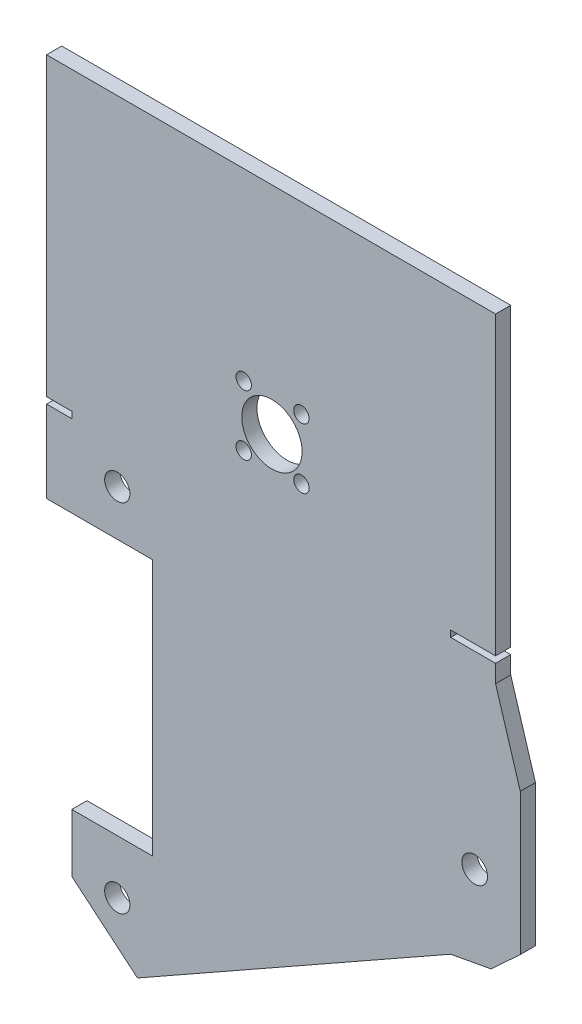
SolidWorks part; units mm, degrees
ref_plane "Front Plane" through (0, 0, 0) normal (0, 0, 1) x (1, 0, 0)
ref_plane "Top Plane" through (0, 0, 0) normal (0, 1, 0) x (1, 0, 0)
ref_plane "Right Plane" through (0, 0, 0) normal (1, 0, 0) x (0, 0, -1)
sketch "Sketch1" plane through (0, 0, 0) normal (0, 0, 1) x (1, 0, 0)
  line L0 (0, 0) -> (88.9, 0)
  line L1 (88.9, 0) -> (88.9, -3.5)
  line L2 (88.9, -3.5) -> (93.7917, -19.5)
  line L3 (93.7917, -19.5) -> (93.7917, -47.5)
  line L4 (0, 0) -> (0, -16.2)
  line L5 (0, -16.2) -> (21, -16.2)
  line L6 (21, -16.2) -> (21, -67)
  line L7 (21, -67) -> (5, -67)
  line L8 (5, -67) -> (5, -78.5)
  line L9 (5, -78.5) -> (18, -89.4083)
  line L10 (18, -89.4083) -> (80, -54.3304)
  line L11 (80, -54.3304) -> (88, -52.8477)
  line L12 (88, -52.8477) -> (93.7917, -47.5)
  dimension "D1" = 88.9
  dimension "D2" = 3.5
  dimension "D3" = 163
  dimension "D4" = 16
  dimension "D5" = 28
  dimension "D6" = 89.4083
  dimension "D7" = 21
  dimension "D8" = 50.8
  dimension "D9" = 16
  dimension "D10" = 11.5
  dimension "D11" = 130
  dimension "D12" = 13
  dimension "D13" = 110.5
  dimension "D14" = 62
  dimension "D15" = 8
  dimension "D16" = 161
extrude "Boss-Extrude1" add sketch "Sketch1" along normal blind 3
sketch "Sketch2" plane through (0, 0, 0) normal (0, 1, 0) x (1, 0, 0)
  line L0 (45.8978, 14) -> (40.3978, 14) construction
  line L1 (0, -3) -> (88.9, -3)
  line L2 (0, -3) -> (0, 54)
  line L3 (0, 54) -> (88.9, 54)
  line L4 (88.9, -3) -> (88.9, 54)
  circle A0 centre (40.3978, 8.5) radius 1.5
  circle A1 centre (40.3978, 20) radius 1.5
  circle A2 centre (51.8978, 8.5) radius 1.5
  circle A3 centre (51.8978, 20) radius 1.5
  ellipse E0 centre (45.8978, 14) end of major axis (45.8978, 8) minor radius 5.5
  dimension "D9" = 3
  dimension "D10" = 3
  dimension "D11" = 3
  dimension "D12" = 3
  dimension "D1" = 88.9
  dimension "D2" = 57
  dimension "D3" = 45.8978
  dimension "D4" = 5.5
  dimension "D5" = 11.5
  dimension "D6" = 23
  dimension "D7" = 11.5
  dimension "D8" = 17
  dimension "D13" = 12
  dimension "D14" = 11
extrude "Boss-Extrude2" add sketch "Sketch2" along normal blind 3
ref_plane "Plane1" through (85.9, 0, 0) normal (1, 0, 0) x (0, 0, -1)
sketch "Sketch3" plane through (85.9, 0, 0) normal (1, 0, 0) x (0, 0, -1)
  line L0 (11.5, 0) -> (0, 0)
  line L1 (0, 0) -> (54, 0) construction
  line L2 (0, 0) -> (0, -11.5)
  line L3 (0, -19.5) -> (0, -3.5) construction
  line L4 (0, -11.5) -> (11.5, 0)
  dimension "D1" = 11.5
  dimension "D2" = 11.5
extrude "Boss-Extrude3" add sketch "Sketch3" against normal blind 84.5
sketch "Sketch4" plane through (0, 0, 0) normal (0, 0, -1) x (-1, 0, 0)
  line L0 (-1.4, -11.5) -> (-85.9, -11.5) construction
  line L1 (-81.4, -11.5) -> (-6.4, -11.5)
  line L2 (-81.4, -11.5) -> (-81.4, 0)
  line L3 (-81.4, 0) -> (-6.4, 0)
  line L4 (-6.4, -11.5) -> (-6.4, 0)
  line L5 (-50.8976, 0) -> (-85.9, 0) construction
  line L6 (-85.9, 13.7659) -> (-85.9, -13.7659) construction
  dimension "D1" = 75
  dimension "D2" = 4.5
extrude "Cut-Extrude2" cut sketch "Sketch4" along normal blind 84.5
sketch "Sketch6" plane through (0, 0, 3) normal (0, 0, 1) x (1, 0, 0)
  line L0 (0, 3) -> (0, -16.2) construction
  line L1 (0, 3) -> (88.9, 3) construction
  circle A0 centre (14, -77.66) radius 2.5
  circle A1 centre (84.763, -37.386) radius 2.54
  circle A2 centre (14, -7.16) radius 2.5
  dimension "D1" = 5
  dimension "D2" = 5
  dimension "D3" = 5.08
  dimension "D4" = 14
  dimension "D5" = 10.16
  dimension "D6" = 70.5
  dimension "D7" = 14
  dimension "D8" = 40.386
  dimension "D9" = 70.763
extrude "Cut-Extrude3" cut sketch "Sketch6" against normal blind 84.5
sketch "Sketch7" plane through (0, 0, 0) normal (0, -1, 0) x (1, 0, 0)
  line L1 (88.9, -54) -> (0, -54)
  line L2 (88.9, -54) -> (88.9, 0)
  line L3 (88.9, 0) -> (0, 0)
  line L4 (0, -54) -> (0, 0)
extrude "Cut-Extrude4" cut sketch "Sketch7" against normal through all both and the other way through all
sketch "Sketch8" plane through (0, 0, 0) normal (0, 0, -1) x (-1, 0, 0)
  line L0 (-88.9, 3) -> (0, 3) construction
  line L1 (-88.9, 3) -> (0, 3)
  line L2 (-88.9, 3) -> (-88.9, 59.896)
  line L3 (-88.9, 59.896) -> (0, 59.896)
  line L4 (0, 3) -> (0, 59.896)
  line L5 (-44.619, 17.1375) -> (-38.65, 17.1375) construction
  line L6 (-14, -77.66) -> (-84.763, -77.66) construction
  line L7 (-84.763, -77.66) -> (-84.763, -37.386) construction
  line L8 (-49.3815, -77.66) -> (-49.3815, 51.3441) construction
  line L9 (-58.3815, 3) -> (-58.3815, 17.1375) construction
  line L10 (-58.3815, 17.1375) -> (-44.619, 17.1375) construction
  circle A0 centre (-44.619, 17.1375) radius 5.969
  circle A1 centre (-39.031, 23.4875) radius 1.524
  circle A2 centre (-39.031, 11.5495) radius 1.524
  circle A3 centre (-50.461, 23.4875) radius 1.524
  circle A4 centre (-50.461, 11.5495) radius 1.524
  dimension "D8" = 11.938
  dimension "D9" = 3.048
  dimension "D10" = 3.048
  dimension "D11" = 3.048
  dimension "D12" = 3.048
  dimension "D1" = 56.896
  dimension "D2" = 88.9
  dimension "D3" = 14.1375
  dimension "D4" = 5.588
  dimension "D5" = 4.7625
  dimension "D6" = 11.938
  dimension "D7" = 5.588
  dimension "D14" = 11.43
extrude "Boss-Extrude4" add sketch "Sketch8" against normal up to surface (3 mm away) up to face at (16.5, -77.66, 3)
sketch "Sketch10" plane through (0, 0, 0) normal (0, 0, -1) x (-1, 0, 0)
  line L0 (-88.9, -3.5) -> (-88.9, 59.896) construction
  line L1 (0, 0) -> (-5.08, 0)
  line L2 (0, 0) -> (0, 1.27)
  line L3 (0, 1.27) -> (-5.08, 1.27)
  line L4 (-5.08, 0) -> (-5.08, 1.27)
  line L5 (-80.01, 0) -> (-88.9, 0)
  line L6 (-80.01, 0) -> (-80.01, 1.27)
  line L7 (-80.01, 1.27) -> (-88.9, 1.27)
  line L8 (-88.9, 0) -> (-88.9, 1.27)
  dimension "D1" = 5.08
  dimension "D2" = 1.27
  dimension "D3" = 8.89
  dimension "D4" = 1.27
extrude "Cut-Extrude5" cut sketch "Sketch10" against normal blind 10
